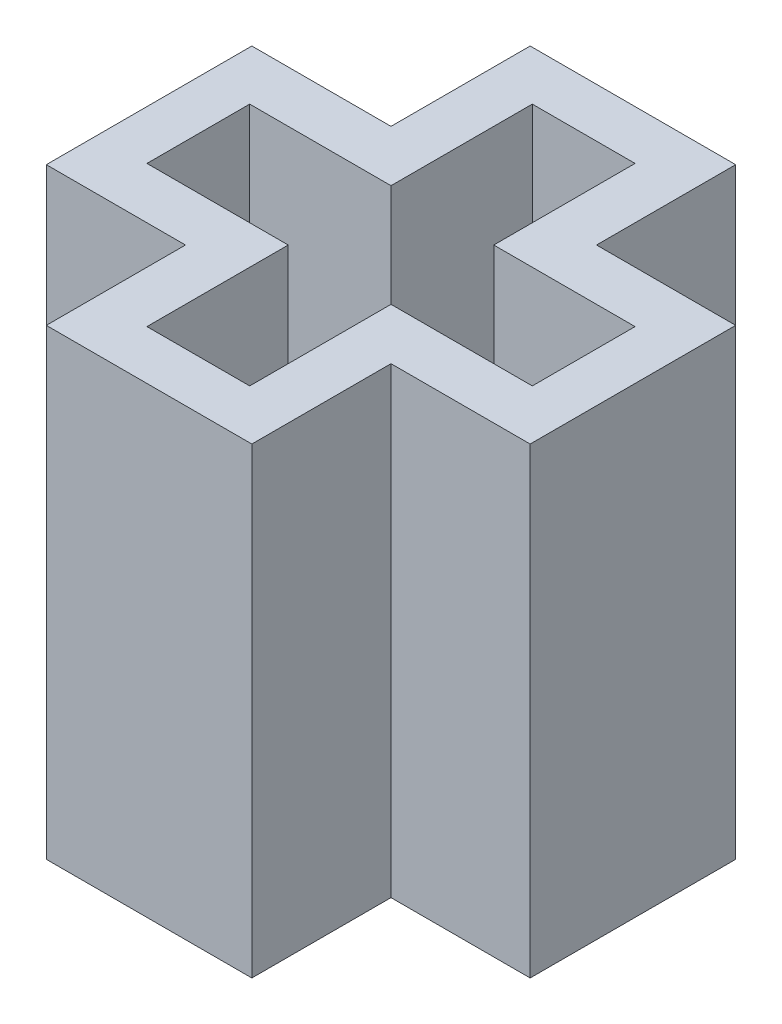
SolidWorks part; units mm, degrees
ref_plane "Front Plane" through (0, 0, 0) normal (0, 0, 1) x (1, 0, 0)
ref_plane "Top Plane" through (0, 0, 0) normal (0, 1, 0) x (1, 0, 0)
ref_plane "Right Plane" through (0, 0, 0) normal (1, 0, 0) x (0, 0, -1)
ref_axis "Axis1" through (0, 0, -39.8625) along (0, 0, 1)
ref_axis "Axis2" through (0, -40.0743, 0) along (0, 1, 0)
ref_axis "Axis3" through (48.4474, 0, 0) along (-1, 0, 0)
sketch "Sketch1" plane through (0, 0, 0) normal (0, 1, 0) x (1, 0, 0)
  line L0 (0, 39.8625) -> (0, -47.0489) construction
  line L5 (-1.2, 2.825) -> (1.2, 2.825)
  line L18 (-1.2, 2.825) -> (-1.2, 1.2)
  line L19 (-1.2, -2.825) -> (1.2, -2.825)
  line L20 (1.2, 2.825) -> (1.2, 1.2)
  line L22 (2.825, 1.2) -> (1.2, 1.2)
  line L27 (2.825, 1.2) -> (2.825, -1.2)
  line L28 (2.825, -1.2) -> (1.2, -1.2)
  line L29 (-2.825, 1.2) -> (-2.825, -1.2)
  line L36 (1.2, -2.825) -> (1.2, -1.2)
  line L37 (1.2, -2.825) -> (-1.2, -2.825)
  line L38 (-1.2, -2.825) -> (-1.2, -1.2)
  line L39 (1.2, 2.825) -> (-1.2, 2.825)
  line L45 (-0.6, 2.25) -> (0.6, 2.25)
  line L46 (-0.6, -2.25) -> (0.6, -2.25)
  line L47 (-0.6, 2.25) -> (-0.6, 0.6)
  line L48 (-0.6, 0.6) -> (-2.25, 0.6)
  line L49 (-2.25, 0.6) -> (-2.25, -0.6)
  line L50 (-2.25, -0.6) -> (-0.6, -0.6)
  line L51 (-0.6, -0.6) -> (-0.6, -2.25)
  line L52 (0.6, -2.25) -> (0.6, -0.6)
  line L53 (-2.825, -1.2) -> (-1.2, -1.2)
  line L54 (-2.825, -1.2) -> (-2.825, 1.2)
  line L55 (-2.825, 1.2) -> (-1.2, 1.2)
  line L56 (2.825, -1.2) -> (2.825, 1.2)
  line L62 (0.6, -0.6) -> (2.25, -0.6)
  line L63 (2.25, -0.6) -> (2.25, 0.6)
  line L64 (2.25, 0.6) -> (0.6, 0.6)
  line L65 (0.6, 0.6) -> (0.6, 2.25)
  line L66 (-0.6, 0.6) -> (0.6, -0.6) construction
  line L69 (-1.2, 1.2) -> (-2.825, 1.2)
  line L70 (1.2, 1.2) -> (2.825, 1.2)
  line L72 (-1.2, 1.2) -> (-1.2, 2.825)
  line L73 (1.2, -1.2) -> (1.2, -2.825)
  line L74 (1.2, 1.2) -> (1.2, 2.825)
  line L75 (-1.2, -1.2) -> (-2.825, -1.2)
  line L76 (1.2, -1.2) -> (2.825, -1.2)
  line L77 (-1.2, -1.2) -> (-1.2, -2.825)
  point P4 (0, 2.825)
  point P9 (0, 2.25)
  point P14 (0, -2.25)
  point P31 (0, 0)
  point P32 (0, 0)
  point P33 (2, 1)
  dimension "D1" = 2.4
  dimension "D2" = 5.65
  dimension "D3" = 4.5
  dimension "D4" = 1.2
  dimension "D5" = 4
extrude "Boss-Extrude1" add sketch "Sketch1" along normal blind 5.4 contours L19 L5 region at (0, 0, -2.7451)
